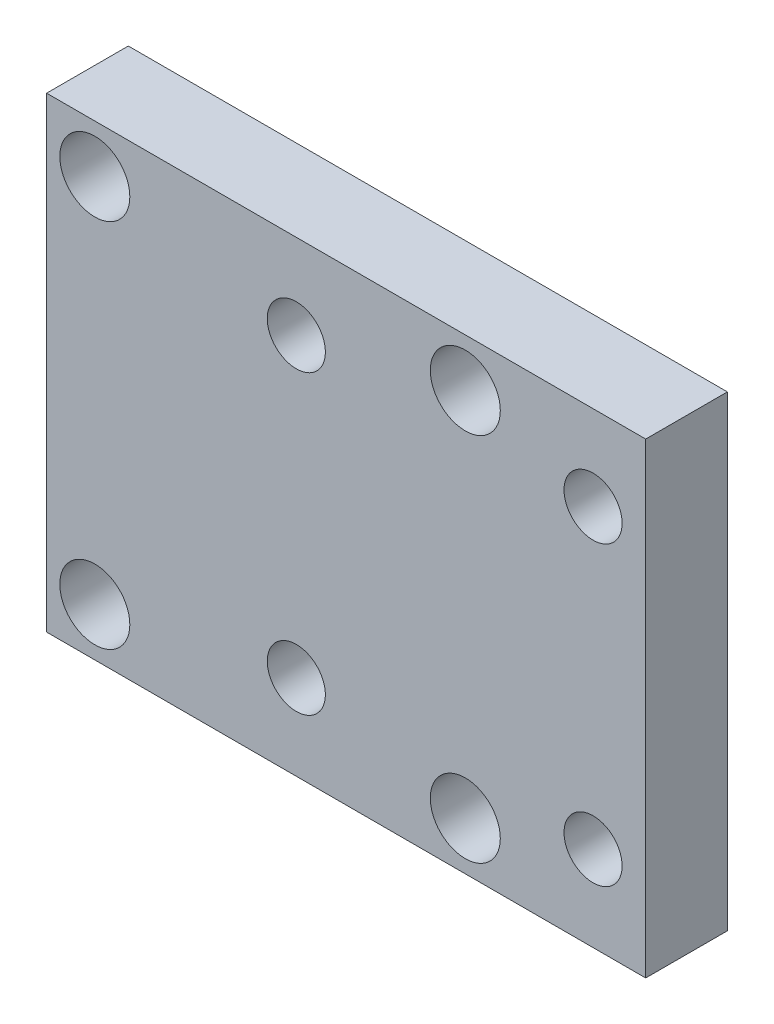
SolidWorks part; units mm, degrees
ref_plane "Front Plane" through (0, 0, 0) normal (0, 0, 1) x (1, 0, 0)
ref_plane "Top Plane" through (0, 0, 0) normal (0, 1, 0) x (1, 0, 0)
ref_plane "Right Plane" through (0, 0, 0) normal (1, 0, 0) x (0, 0, -1)
sketch "Sketch1" plane through (0, 0, 0) normal (0, 0, 1) x (1, 0, 0)
  line L1 (-14.09, 0) -> (-65.43, 0)
  line L2 (-14.09, 0) -> (-14.09, -40)
  line L3 (-14.09, -40) -> (-65.43, -40)
  line L4 (-65.43, 0) -> (-65.43, -40)
  dimension "D1" = 51.34
  dimension "D2" = 40
extrude "Boss-Extrude1" add sketch "Sketch1" along normal blind 7
sketch "Sketch2" plane through (0, 0, 0) normal (0, 0, 1) x (1, 0, 0)
  line L4 (-65.43, 0) -> (-65.43, -40) construction
  line L6 (-65.43, -40) -> (-14.09, -40) construction
  circle A6 centre (-61.3, -35.875) radius 2
  circle A7 centre (-29.55, -35.875) radius 2
  circle A8 centre (-29.55, -4.125) radius 2
  circle A9 centre (-61.3, -4.125) radius 2
  dimension "D1" = 31.75
  dimension "D2" = 31.75
  dimension "D3" = 4.13
  dimension "D4" = 4
  dimension "D5" = 4.125
  dimension "D6" = 2
  dimension "D7" = 2
extrude "Cut-Extrude2" cut sketch "Sketch2" along normal through all
sketch "Sketch8" plane through (0, 0, 7) normal (0, 0, 1) x (1, 0, 0)
  circle A0 centre (-61.3, -4.125) radius 3
  circle A3 centre (-29.55, -4.125) radius 3
  circle A4 centre (-29.55, -35.875) radius 3
  circle A5 centre (-61.3, -35.875) radius 3
  dimension "D1" = 6
  dimension "D2" = 2
  dimension "D3" = 2
extrude "Cut-Extrude6" cut sketch "Sketch8" against normal blind 6
sketch "Sketch9" plane through (0, 0, 7) normal (0, 0, 1) x (1, 0, 0)
  line L0 (-18.6008, -7.27) -> (-18.6008, -43.6541) construction
  line L1 (-18.6008, -7.27) -> (-44.0308, -7.27) construction
  line L2 (-44.0308, -7.27) -> (-44.0308, -32.7) construction
  line L3 (-44.0308, -32.7) -> (-18.6008, -32.7) construction
  circle A0 centre (-44.0308, -7.27) radius 2.49
  circle A1 centre (-18.6008, -7.27) radius 2.49
  circle A2 centre (-44.0308, -32.7) radius 2.49
  circle A3 centre (-18.6008, -32.7) radius 2.49
  point P0 (0, 0)
  dimension "D2" = 25.43
  dimension "D3" = 25.43
  dimension "D4" = 2
  dimension "D5" = 2
extrude "Cut-Extrude7" cut sketch "Sketch9" against normal up to surface (7 mm away) up to face at (-27.55, -4.125, 0)
equation "\"hole_screw_1_4_20\"= 6"
equation "\"inch\"=25.43"
